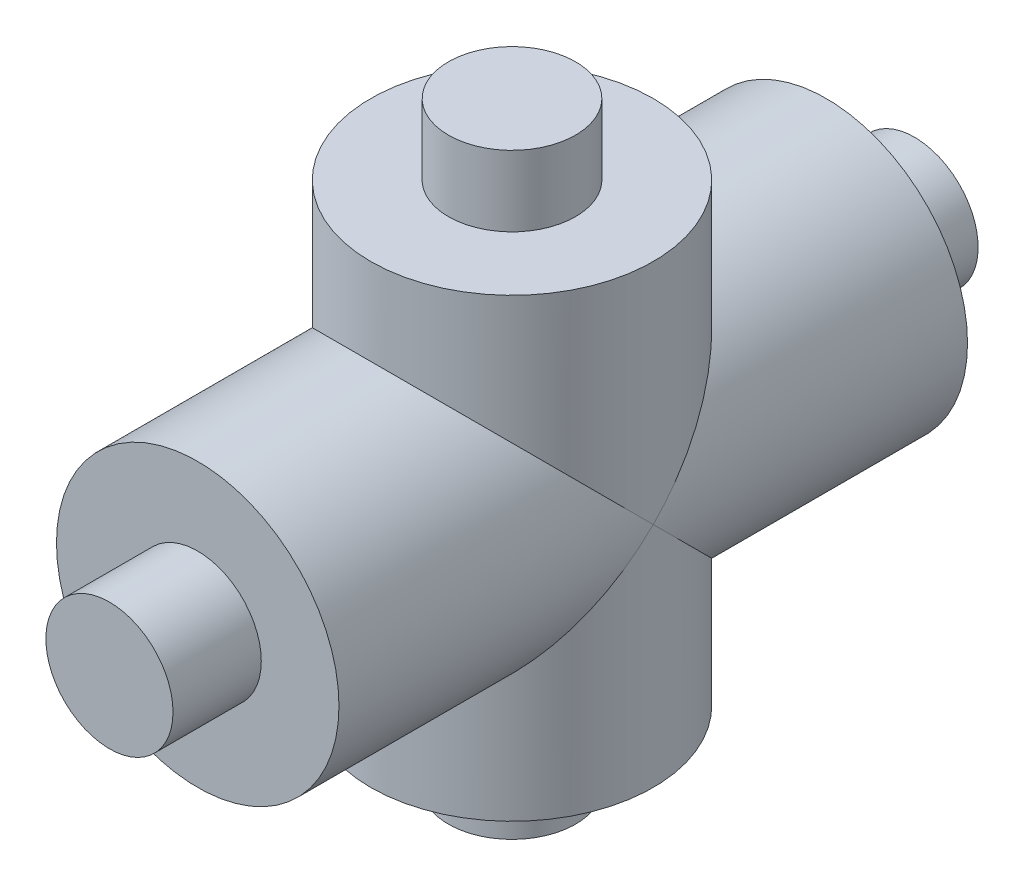
SolidWorks part; units mm, degrees
ref_plane "前视基准面" through (0, 0, 0) normal (0, 0, 1) x (1, 0, 0)
ref_plane "上视基准面" through (0, 0, 0) normal (0, 1, 0) x (1, 0, 0)
ref_plane "右视基准面" through (0, 0, 0) normal (1, 0, 0) x (0, 0, -1)
sketch "草图1" plane through (0, 0, 0) normal (0, 0, 1) x (1, 0, 0)
  circle A0 centre (0, 0) radius 4
extrude "凸台-拉伸1" add sketch "草图1" along normal blind 17.8
sketch "草图2" plane through (0, 0, 17.8) normal (0, 0, 1) x (1, 0, 0)
  circle A0 centre (0, 0) radius 1.8
extrude "凸台-拉伸2" add sketch "草图2" along normal blind 2.5
sketch "草图3" plane through (0, 0, 0) normal (0, 0, -1) x (-1, 0, 0)
  circle A0 centre (0, 0) radius 1.8
extrude "凸台-拉伸3" add sketch "草图3" along normal blind 2.5
sketch "草图4" plane through (0, 0, 0) normal (0, 1, 0) x (1, 0, 0)
  circle A0 centre (0, -8.9) radius 4
extrude "凸台-拉伸4" add sketch "草图4" along normal blind 6.45 and the other way blind 6.45
sketch "草图5" plane through (0, -6.45, 0) normal (0, -1, 0) x (-1, 0, 0)
  circle A0 centre (0, -8.9) radius 1.8
extrude "凸台-拉伸5" add sketch "草图5" along normal blind 2
sketch "草图6" plane through (0, 6.45, 0) normal (0, 1, 0) x (1, 0, 0)
  circle A0 centre (0, -8.9) radius 1.8
extrude "凸台-拉伸6" add sketch "草图6" along normal blind 2
